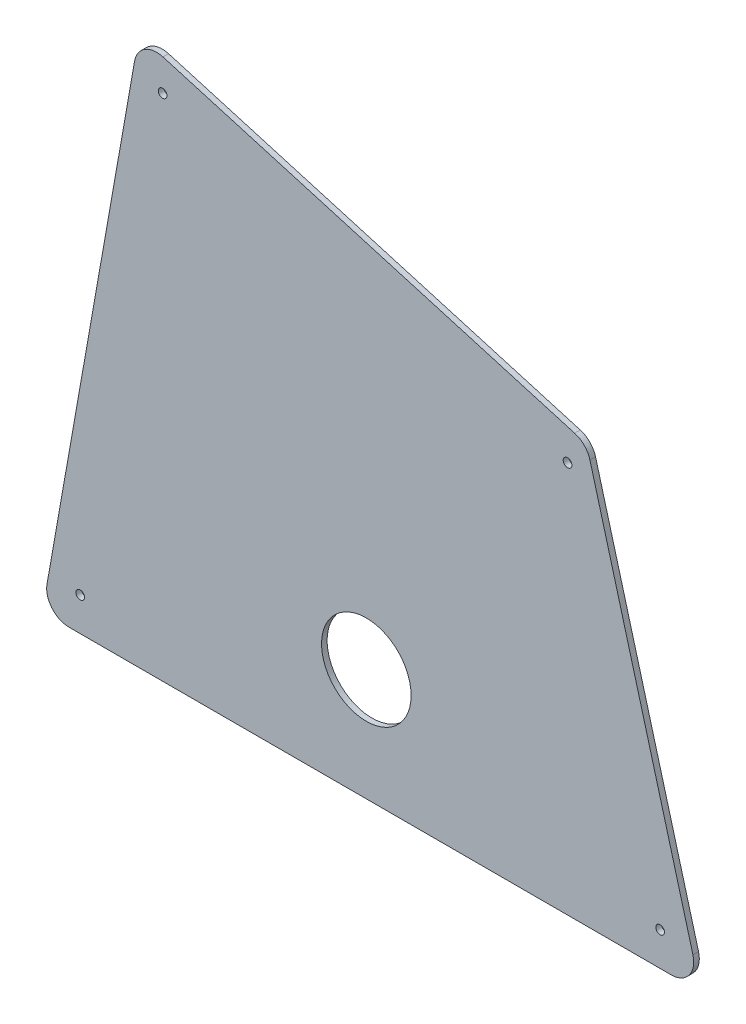
SolidWorks part; units mm, degrees
material "PC High Viscosity"
ref_plane "Front Plane" through (0, 0, 0) normal (0, 0, 1) x (1, 0, 0)
ref_plane "Top Plane" through (0, 0, 0) normal (0, 1, 0) x (1, 0, 0)
ref_plane "Right Plane" through (0, 0, 0) normal (1, 0, 0) x (0, 0, -1)
sketch "Sketch1" plane through (0, 0, 0) normal (0, 0, 1) x (1, 0, 0)
  line L0 (-115.3996, 121.8569) -> (118.1755, 53.7759)
  line L1 (-168.6745, -185.018) -> (173.0582, -185.018)
  line L2 (-181.1816, -170.1127) -> (-131.4605, 111.8696)
  line L4 (185.3093, -168.9711) -> (126.8727, 44.9302)
  line L5 (-183.8098, -185.018) -> (124.9995, 125.8211) construction
  line L6 (-129.0005, 125.8211) -> (189.6932, -185.018) construction
  arc A0 (-168.6745, -185.018) -> (-181.1816, -170.1127) centre (-168.6745, -172.318) cw
  arc A1 (173.0582, -185.018) -> (185.3093, -168.9711) centre (173.0582, -172.318) ccw
  arc A2 (118.1755, 53.7759) -> (126.8727, 44.9302) centre (114.6217, 41.5833) cw
  arc A3 (-131.4605, 111.8696) -> (-115.3996, 121.8569) centre (-118.9535, 109.6642) cw
  circle A4 centre (0, -121.518) radius 25.4
  point P0 (0, 0)
  point P15 (0, 0)
  point P19 (124.9995, 51.7869)
  dimension "D3" = 12.7
  dimension "D5" = 12.7
  dimension "D8" = 50.8
  dimension "D1" = 254
  dimension "D2" = 317.5
  dimension "D4" = 16.25
  dimension "D6" = 80
  dimension "D7" = 74.72
  dimension "D9" = 63.5
extrude "Boss-Extrude1" add sketch "Sketch1" along normal blind 3.175
sketch "Sketch3" plane through (0, 0, 3.175) normal (0, 0, 1) x (1, 0, 0)
  line L0 (-168.6745, -185.018) -> (173.0582, -185.018) construction
  point P0 (-162.3245, -165.968)
  point P1 (166.7082, -165.968)
  point P2 (114.1727, 37.232)
  point P3 (-115.5855, 103.907)
  dimension "D1" = 19.05
  dimension "D2" = 288.925
  dimension "D3" = 222.25
  dimension "D4" = 6.35
  dimension "D5" = 6.35
  dimension "D6" = 15.875
  dimension "D7" = 12.7
hole_wizard "#10 (0.1935) Diameter Hole1" positions "Sketch6" profile "Sketch7" hole size "#10" standard "ANSI Inch" end condition through all
sketch "Sketch6" plane through (0, 0, 3.175) normal (0, 0, 1) x (1, 0, 0)
  point P0 (-115.5855, 103.907)
  point P3 (114.1727, 37.232)
  point P6 (166.7082, -165.968)
  point P9 (-162.3245, -165.968)
sketch "Sketch7" plane through (-115.5855, 103.907, 3.175) normal (1, 0, 0) x (0, -1, 0)
  line L0 (0, 0) -> (0, 3.175)
  line L1 (0, 3.175) -> (2.4574, 3.175)
  line L2 (2.4574, 3.175) -> (2.4574, 0)
  line L5 (2.4574, 0) -> (0, 0)
  line L11 (0, -6.35) -> (0, 107.95) construction
  dimension "Thru Hole Dia." = 4.9149
  dimension "Thru Hole Depth" = 3.175
